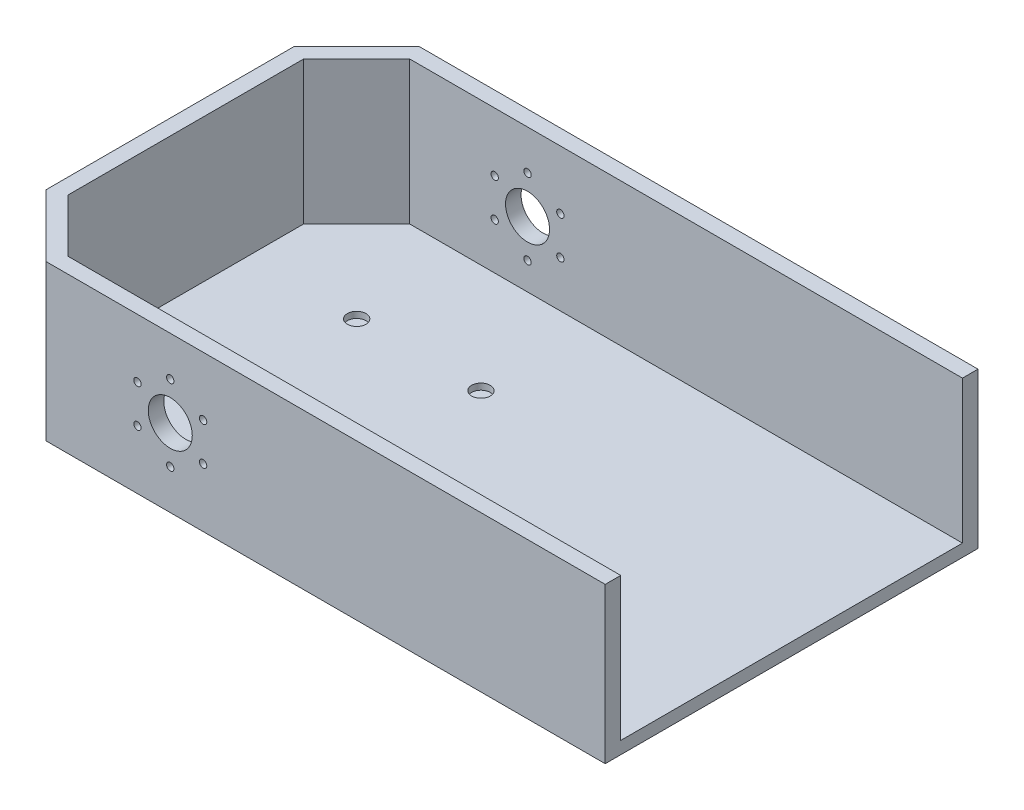
SolidWorks part; units mm, degrees
ref_plane "Front Plane" through (0, 0, 0) normal (0, 0, 1) x (1, 0, 0)
ref_plane "Top Plane" through (0, 0, 0) normal (0, 1, 0) x (1, 0, 0)
ref_plane "Right Plane" through (0, 0, 0) normal (1, 0, 0) x (0, 0, -1)
sketch "Sketch2" plane through (0, 0, 0) normal (0, 1, 0) x (1, 0, 0)
  line L1 (-127, 76.2) -> (127, 76.2)
  line L2 (-127, 76.2) -> (-127, -76.2)
  line L3 (-127, -76.2) -> (127, -76.2)
  line L4 (127, 76.2) -> (127, -76.2)
  point P7 (-207.0779, 155.3084)
  dimension "D1" = 254
  dimension "D2" = 152.4
  dimension "D3" = 76.2
  dimension "D4" = 127
extrude "Boss-Extrude1" add sketch "Sketch2" along normal blind 5.08
chamfer "Chamfer1" distance 25.4 angle 45 2 edges at (-127, 2.54, -76.2) (-127, 2.54, 76.2)
sketch "Sketch4" plane through (0, 5.08, 0) normal (0, 1, 0) x (1, 0, 0)
  line L0 (120.65, 69.85) -> (-98.9697, 69.85)
  line L1 (-98.9697, 69.85) -> (-120.65, 48.1697)
  line L2 (-120.65, 48.1697) -> (-120.65, -48.1697)
  line L3 (-120.65, -48.1697) -> (-98.9697, -69.85)
  line L4 (-98.9697, -69.85) -> (120.65, -69.85)
  line L6 (127, 76.2) -> (-101.6, 76.2)
  line L7 (-101.6, 76.2) -> (-127, 50.8)
  line L8 (-127, 50.8) -> (-127, -50.8)
  line L9 (-127, -50.8) -> (-101.6, -76.2)
  line L10 (-101.6, -76.2) -> (127, -76.2)
  line L11 (127, -76.2) -> (127, 76.2)
  line L12 (127, 76.2) -> (-101.6, 76.2)
  line L13 (-101.6, 76.2) -> (-127, 50.8)
  line L14 (-127, 50.8) -> (-127, -50.8)
  line L15 (-127, -50.8) -> (-101.6, -76.2)
  line L16 (-101.6, -76.2) -> (127, -76.2)
  line L17 (127, -76.2) -> (127, -69.85)
  line L18 (120.65, 69.85) -> (127, 69.85)
  line L19 (120.65, -69.85) -> (127, -69.85)
  line L20 (127, 69.85) -> (127, 76.2)
  line L21 (127, -76.2) -> (127, 76.2) construction
  line L22 (120.65, -69.85) -> (120.65, 69.85) construction
  dimension "D2" = 6.35
  dimension "D1" = 0
extrude "Boss-Extrude3" add sketch "Sketch4" along normal blind 58.42
sketch "Sketch5" plane through (0, 0, 76.2) normal (0, 0, 1) x (1, 0, 0)
  line L0 (-150.3871, 38.1) -> (157.7429, 38.1) construction
  line L1 (-101.6, 0) -> (127, 0) construction
  line L2 (0, -14.9262) -> (0, 83.7522) construction
  line L3 (-50.8, 49.8289) -> (-50.8, 11.4994) construction
  line L5 (-71.0506, 31.75) -> (-33.7726, 31.75) construction
  circle A0 centre (-50.8, 31.75) radius 9
  circle A1 centre (-50.8, 31.75) radius 15.5 construction
  circle A2 centre (-50.8, 47.25) radius 1.5
  circle A3 centre (-37.3766, 39.5) radius 1.5
  circle A4 centre (-37.3766, 24) radius 1.5
  circle A5 centre (-50.8, 16.25) radius 1.5
  circle A6 centre (-64.2234, 24) radius 1.5
  circle A7 centre (-64.2234, 39.5) radius 1.5
  dimension "D2" = 18
  dimension "D5" = 31
  dimension "D6" = 3
  dimension "D1" = 38.1
  dimension "D3" = 50.8
  dimension "D4" = 6.35
  dimension "D7" = 6
extrude "Cut-Extrude1" cut sketch "Sketch5" against normal through all
sketch "Sketch7" plane through (0, 5.08, 0) normal (0, 1, 0) x (1, 0, 0)
  line L0 (33.4878, 0) -> (-147.4125, 0) construction
  line L1 (-76.2, 25.4) -> (-25.4, 25.4) construction
  line L2 (-76.2, 25.4) -> (-76.2, -25.4) construction
  line L3 (-76.2, -25.4) -> (-25.4, -25.4) construction
  line L4 (-25.4, 25.4) -> (-25.4, -25.4) construction
  line L5 (-50.8, 72.7262) -> (-50.8, -86.6673) construction
  circle A0 centre (-76.2, 25.4) radius 3.81
  circle A1 centre (-25.4, 25.4) radius 3.81
  circle A2 centre (-25.4, -25.4) radius 3.81
  circle A3 centre (-76.2, -25.4) radius 3.81
  dimension "D6" = 7.62
  dimension "D7" = 7.62
  dimension "D8" = 7.62
  dimension "D9" = 7.62
  dimension "D1" = 50.8
  dimension "D2" = 50.8
  dimension "D3" = 25.4
  dimension "D4" = 25.4
  dimension "D5" = 50.8
extrude "Cut-Extrude2" cut sketch "Sketch7" against normal blind 2.54 contours A0 | A1 | A2 | A3
